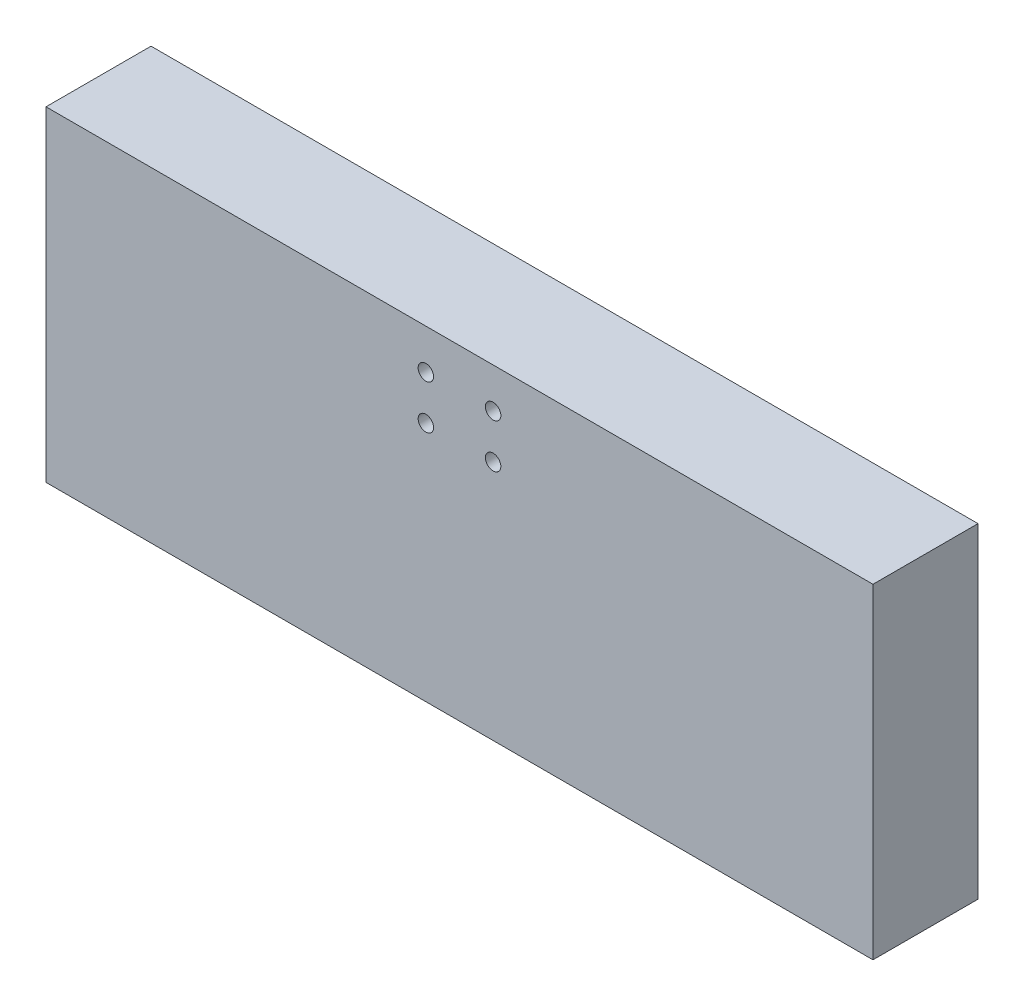
SolidWorks part; units mm, degrees
ref_plane "Front" through (0, 0, 0) normal (0, 0, 1) x (1, 0, 0)
ref_plane "Top" through (0, 0, 0) normal (0, 1, 0) x (1, 0, 0)
ref_plane "Right" through (0, 0, 0) normal (1, 0, 0) x (0, 0, -1)
sketch "Sketch1" plane through (0, 0, 0) normal (0, 1, 0) x (1, 0, 0)
  line L1 (-75, -75) -> (75, -75)
  line L2 (-75, -75) -> (-75, 75)
  line L3 (-75, 75) -> (75, 75)
  line L4 (75, -75) -> (75, 75)
  line L5 (-75, -75) -> (75, 75) construction
  line L6 (-75, 75) -> (75, -75) construction
  point P0 (0, 0)
  dimension "D1" = 150
  dimension "D2" = 150
extrude "Boss-Extrude1" add sketch "Sketch1" against normal blind 59
sketch "Sketch2" plane through (0, 0, 0) normal (0, 1, 0) x (1, 0, 0)
  line L1 (-55.95, -55.95) -> (55.95, -55.95)
  line L2 (-55.95, -55.95) -> (-55.95, 55.95)
  line L3 (-55.95, 55.95) -> (55.95, 55.95)
  line L4 (55.95, -55.95) -> (55.95, 55.95)
  line L5 (-55.95, -55.95) -> (55.95, 55.95) construction
  line L6 (-55.95, 55.95) -> (55.95, -55.95) construction
  point P0 (0, 0)
  dimension "D1" = 111.9
  dimension "D2" = 111.9
extrude "Cut-Extrude1" cut sketch "Sketch2" against normal through all
ref_axis "Axis1" through (0, 0, 0) along (0, -1, 0)
sketch "Sketch9" plane through (-75, 0, 0) normal (-1, 0, 0) x (0, 0, 1)
  line L0 (-75, 0) -> (75, 0) construction
  line L1 (0, 0) -> (7.5, 0)
  line L7 (0, 0) -> (-7.5, 0)
  circle A0 centre (-6.1, -7.25) radius 1.4
  circle A1 centre (6.1, -7.25) radius 1.4
  circle A2 centre (6.1, -15.25) radius 1.4
  circle A3 centre (-6.1, -15.25) radius 1.4
  dimension "D4" = 2.8
  dimension "D2" = 7.5
  dimension "D3" = 7.5
  dimension "D5" = 7.25
extrude "Cut-Extrude4" cut sketch "Sketch9" against normal blind 20 contours A0 | A1 | A2 | A3 region at (-75, -7.25, -6.1)
pattern_circular "CirPattern1" count 3 every 90 about axis through (0, 0, 0) along (0, -1, 0) of "Cut-Extrude4" reverse direction yes
sketch "Sketch10" plane through (0, 0, 0) normal (0, 1, 0) x (1, 0, 0)
  line L0 (-55.95, 55.95) -> (55.95, 55.95)
  line L1 (-55.95, 55.95) -> (-55.95, 161.3983)
  line L2 (55.95, 55.95) -> (55.95, 161.3983)
  line L3 (-55.95, 161.3983) -> (55.95, 161.3983)
extrude "Cut-Extrude6" cut sketch "Sketch10" against normal through all
sketch "Sketch12" plane through (0, 0, 0) normal (0, 1, 0) x (1, 0, 0)
  line L0 (-75, 75) -> (-75, -75) construction
  line L1 (75, 75) -> (-75, 75)
  line L2 (75, 75) -> (75, -55.95)
  line L3 (75, -55.95) -> (-75, -55.95)
  line L4 (-75, 75) -> (-75, -55.95)
  line L5 (-75, -75) -> (75, -75) construction
  dimension "D1" = 19.05
extrude "Cut-Extrude7" cut sketch "Sketch12" against normal through all
